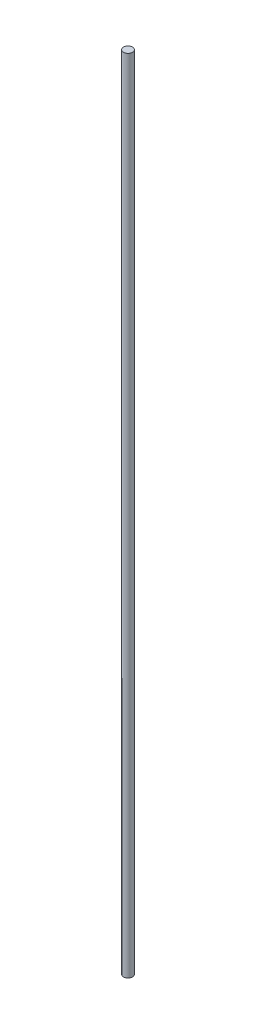
SolidWorks part; units mm, degrees
ref_plane "Front Plane" through (0, 0, 0) normal (0, 0, 1) x (1, 0, 0)
ref_plane "Top Plane" through (0, 0, 0) normal (0, 1, 0) x (1, 0, 0)
ref_plane "Right Plane" through (0, 0, 0) normal (1, 0, 0) x (0, 0, -1)
sketch "Sketch1" plane through (0, 0, 0) normal (0, 1, 0) x (1, 0, 0)
  circle A0 centre (0, 0) radius 5.08
extrude "Boss-Extrude1" add sketch "Sketch1" along normal blind 901.7
